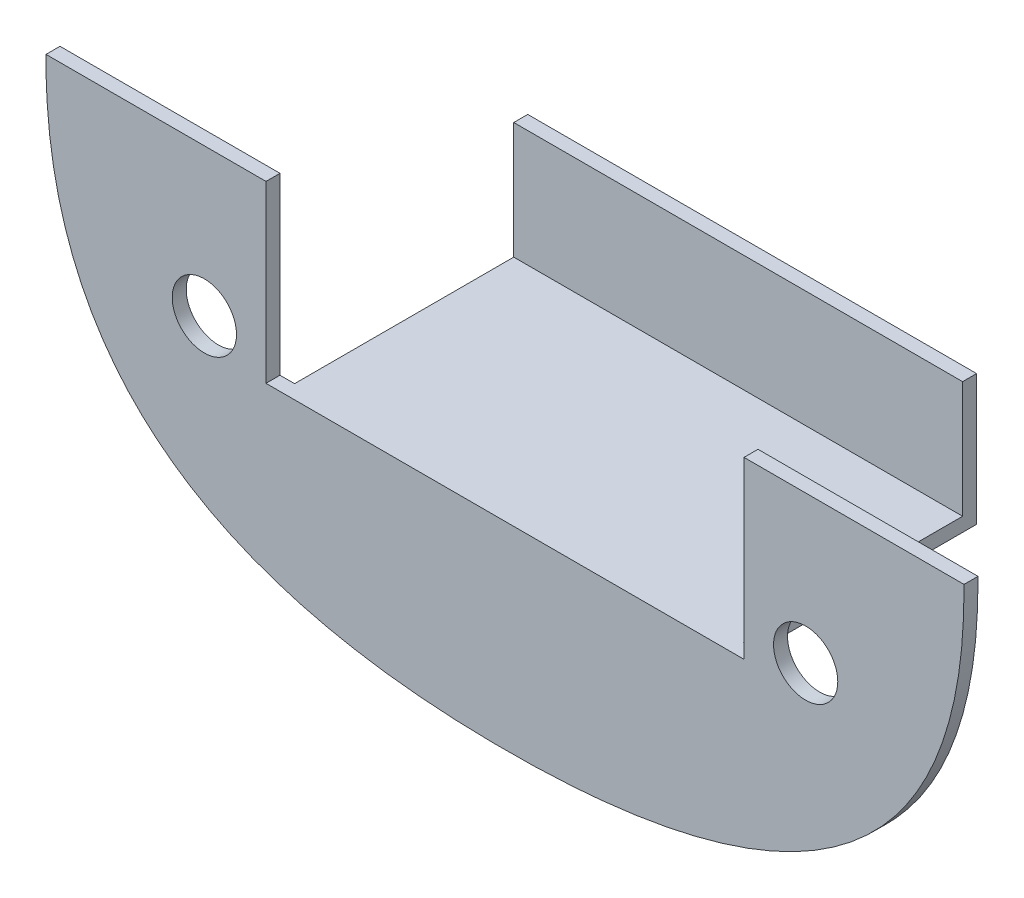
SolidWorks part; units mm, degrees
ref_plane "Front Plane" through (0, 0, 0) normal (0, 0, 1) x (1, 0, 0)
ref_plane "Top Plane" through (0, 0, 0) normal (0, 1, 0) x (1, 0, 0)
ref_plane "Right Plane" through (0, 0, 0) normal (1, 0, 0) x (0, 0, -1)
sketch "Sketch1" plane through (65.5, -188.8754, 24.4234) normal (0, 0, -1) x (-1, 0, 0)
  line L2 (-52.07, -36.8878) -> (52.07, -36.8878)
  line L3 (-52.07, -36.8878) -> (-42.5, -36.8878) construction
  line L4 (42.5, -36.8878) -> (52.07, -36.8878) construction
  line L5 (52.07, -36.8878) -> (52.07, 67.2522) construction
  line L6 (-52.07, -36.8878) -> (-52.07, 67.2522) construction
  line L7 (-52.07, -36.8878) -> (-42.5, -36.8878) construction
  line L8 (42.5, -36.8878) -> (52.07, -36.8878) construction
  line L9 (52.07, -36.8878) -> (52.07, 67.2522) construction
  line L10 (-52.07, -36.8878) -> (-52.07, 67.2522) construction
  line L11 (52.07, -36.8878) -> (52.07, 1.2122)
  line L12 (52.07, 1.2122) -> (100, 1.2122)
  line L13 (-100, 1.2122) -> (-52.07, 1.2122)
  line L14 (-52.07, 1.2122) -> (-52.07, -36.8878)
  circle A0 centre (-65.5, -30.8878) radius 7 construction
  circle A1 centre (-65.5, -30.8878) radius 7
  circle A4 centre (65.5, -30.8878) radius 7 construction
  circle A5 centre (65.5, -30.8878) radius 7
  spline S0 degree 3 poles (-100, 100.5541) (-100, 91.6667) (-100, 75) (-100, 50) (-100, 25) (-100, 8.3333) (-100, -3.0509) (-99.7823, -9.1535) (-98.6814, -18.2496) (-96.6708, -27.1928) (-93.6177, -35.841) (-89.4261, -44.0037) (-84.0794, -51.4648) (-77.6729, -58.0369) (-70.3884, -63.6161) (-62.4486, -68.1997) (-51.2385, -73.0758) (-36.4788, -77.1218) (-18.3084, -79.5568) (-6.1019, -80) (6.1019, -80) (18.3084, -79.5568) (36.4788, -77.1218) (51.2385, -73.0758) (62.4486, -68.1997) (70.3884, -63.6161) (77.6729, -58.0369) (84.0794, -51.4648) (89.4261, -44.0037) (93.6177, -35.841) (96.6708, -27.1928) (98.6814, -18.2496) (99.7823, -9.1535) (100, -3.0509) (100, 8.3333) (100, 25) (100, 50) (100, 75) (100, 91.6667) (100, 100.5541) (99.8835, 101.663) (99.344, 103.2464) (98.4974, 104.6847) (97.0622, 106.3843) (94.8888, 108.1258) (91.9976, 109.7782) (88.9551, 111.1271) (85.8262, 112.2552) (82.6425, 113.2169) (79.4227, 114.0479) (76.1778, 114.7739) (72.9147, 115.4129) (69.6383, 115.979) (65.2561, 116.6501) (59.7591, 117.3544) (53.1437, 118.032) (46.5161, 118.5751) (37.6683, 119.1501) (26.5955, 119.6359) (13.2992, 119.9414) (4.4331, 120) (-4.4331, 120) (-13.2992, 119.9414) (-26.5955, 119.6359) (-37.6683, 119.1501) (-46.5161, 118.5751) (-53.1437, 118.032) (-59.7591, 117.3544) (-65.2561, 116.6501) (-69.6383, 115.979) (-72.9147, 115.4129) (-76.1778, 114.7739) (-79.4227, 114.0479) (-82.6425, 113.2169) (-85.8262, 112.2552) (-88.9551, 111.1271) (-91.9976, 109.7782) (-94.8888, 108.1258) (-97.0622, 106.3843) (-98.4974, 104.6847) (-99.344, 103.2464) (-99.8835, 101.663) (-100, 100.5541) (-100, 91.6667) (-100, 75) knots -0.004712 -0.002356 0 0 0.035426 0.070853 0.106279 0.141706 0.141706 0.154676 0.167646 0.180616 0.193586 0.206556 0.219526 0.232496 0.245467 0.258437 0.271407 0.297347 0.323287 0.349227 0.349227 0.375167 0.401107 0.427048 0.440018 0.452988 0.465958 0.478928 0.491898 0.504868 0.517838 0.530808 0.543778 0.556748 0.556748 0.592175 0.627601 0.663028 0.698454 0.698454 0.70081 0.703166 0.705522 0.707877 0.712589 0.717301 0.722012 0.726724 0.731436 0.736147 0.740859 0.745571 0.750282 0.754994 0.764417 0.773841 0.783264 0.792687 0.811534 0.830381 0.849227 0.849227 0.868074 0.88692 0.905767 0.91519 0.924614 0.934037 0.94346 0.948172 0.952884 0.957595 0.962307 0.967018 0.97173 0.976442 0.981153 0.985865 0.990577 0.992933 0.995288 0.997644 1 1 1.035426 1.070853 1.106279 only from (-100, 100) to (-100, 100) construction
  spline S1 degree 3 poles (-100, 100.5541) (-100, 91.6667) (-100, 75) (-100, 50) (-100, 25) (-100, 8.3333) (-100, -3.0509) (-99.7823, -9.1535) (-98.6814, -18.2496) (-96.6708, -27.1928) (-93.6177, -35.841) (-89.4261, -44.0037) (-84.0794, -51.4648) (-77.6729, -58.0369) (-70.3884, -63.6161) (-62.4486, -68.1997) (-51.2385, -73.0758) (-36.4788, -77.1218) (-18.3084, -79.5568) (-6.1019, -80) (6.1019, -80) (18.3084, -79.5568) (36.4788, -77.1218) (51.2385, -73.0758) (62.4486, -68.1997) (70.3884, -63.6161) (77.6729, -58.0369) (84.0794, -51.4648) (89.4261, -44.0037) (93.6177, -35.841) (96.6708, -27.1928) (98.6814, -18.2496) (99.7823, -9.1535) (100, -3.0509) (100, 8.3333) (100, 25) (100, 50) (100, 75) (100, 91.6667) (100, 100.5541) (99.8835, 101.663) (99.344, 103.2464) (98.4974, 104.6847) (97.0622, 106.3843) (94.8888, 108.1258) (91.9976, 109.7782) (88.9551, 111.1271) (85.8262, 112.2552) (82.6425, 113.2169) (79.4227, 114.0479) (76.1778, 114.7739) (72.9147, 115.4129) (69.6383, 115.979) (65.2561, 116.6501) (59.7591, 117.3544) (53.1437, 118.032) (46.5161, 118.5751) (37.6683, 119.1501) (26.5955, 119.6359) (13.2992, 119.9414) (4.4331, 120) (-4.4331, 120) (-13.2992, 119.9414) (-26.5955, 119.6359) (-37.6683, 119.1501) (-46.5161, 118.5751) (-53.1437, 118.032) (-59.7591, 117.3544) (-65.2561, 116.6501) (-69.6383, 115.979) (-72.9147, 115.4129) (-76.1778, 114.7739) (-79.4227, 114.0479) (-82.6425, 113.2169) (-85.8262, 112.2552) (-88.9551, 111.1271) (-91.9976, 109.7782) (-94.8888, 108.1258) (-97.0622, 106.3843) (-98.4974, 104.6847) (-99.344, 103.2464) (-99.8835, 101.663) (-100, 100.5541) (-100, 91.6667) (-100, 75) knots -0.004712 -0.002356 0 0 0.035426 0.070853 0.106279 0.141706 0.141706 0.154676 0.167646 0.180616 0.193586 0.206556 0.219526 0.232496 0.245467 0.258437 0.271407 0.297347 0.323287 0.349227 0.349227 0.375167 0.401107 0.427048 0.440018 0.452988 0.465958 0.478928 0.491898 0.504868 0.517838 0.530808 0.543778 0.556748 0.556748 0.592175 0.627601 0.663028 0.698454 0.698454 0.70081 0.703166 0.705522 0.707877 0.712589 0.717301 0.722012 0.726724 0.731436 0.736147 0.740859 0.745571 0.750282 0.754994 0.764417 0.773841 0.783264 0.792687 0.811534 0.830381 0.849227 0.849227 0.868074 0.88692 0.905767 0.91519 0.924614 0.934037 0.94346 0.948172 0.952884 0.957595 0.962307 0.967018 0.97173 0.976442 0.981153 0.985865 0.990577 0.992933 0.995288 0.997644 1 1 1.035426 1.070853 1.106279 only from (-100, 100) to (-100, 100)
  dimension "D1" = 38.1
extrude "Boss-Extrude2" add sketch "Sketch1" along normal blind 3.048 contours L13 S1 L12 L11 L2 L14 A1 A5 region at (65.5, -230.692, 24.4234)
sketch "Sketch2" plane through (0, 0, 24.4234) normal (0, 0, 1) x (1, 0, 0)
  line L0 (117.57, -225.7632) -> (13.43, -225.7632) construction
  line L1 (16.605, -225.7632) -> (114.395, -225.7632)
  line L2 (16.605, -225.7632) -> (16.605, -228.8112)
  line L3 (16.605, -228.8112) -> (114.395, -228.8112)
  line L4 (114.395, -225.7632) -> (114.395, -228.8112)
  line L5 (13.43, -225.7632) -> (13.43, -187.6632) construction
  line L6 (117.57, -187.6632) -> (117.57, -225.7632) construction
  dimension "D1" = 3.175
  dimension "D2" = 3.175
  dimension "D3" = 3.048
extrude "Boss-Extrude3" add sketch "Sketch2" against normal blind 53.848 contours L3 L4 L1 L2
sketch "Sketch3" plane through (0, -225.7632, 0) normal (0, 1, 0) x (1, 0, 0)
  line L0 (114.395, 29.4246) -> (114.395, -21.3754) construction
  line L1 (16.605, 29.4246) -> (114.395, 29.4246)
  line L2 (16.605, 29.4246) -> (16.605, 26.3766)
  line L3 (16.605, 26.3766) -> (114.395, 26.3766)
  line L4 (114.395, 29.4246) -> (114.395, 26.3766)
  dimension "D1" = 3.048
extrude "Boss-Extrude4" add sketch "Sketch3" along normal blind 25.4
